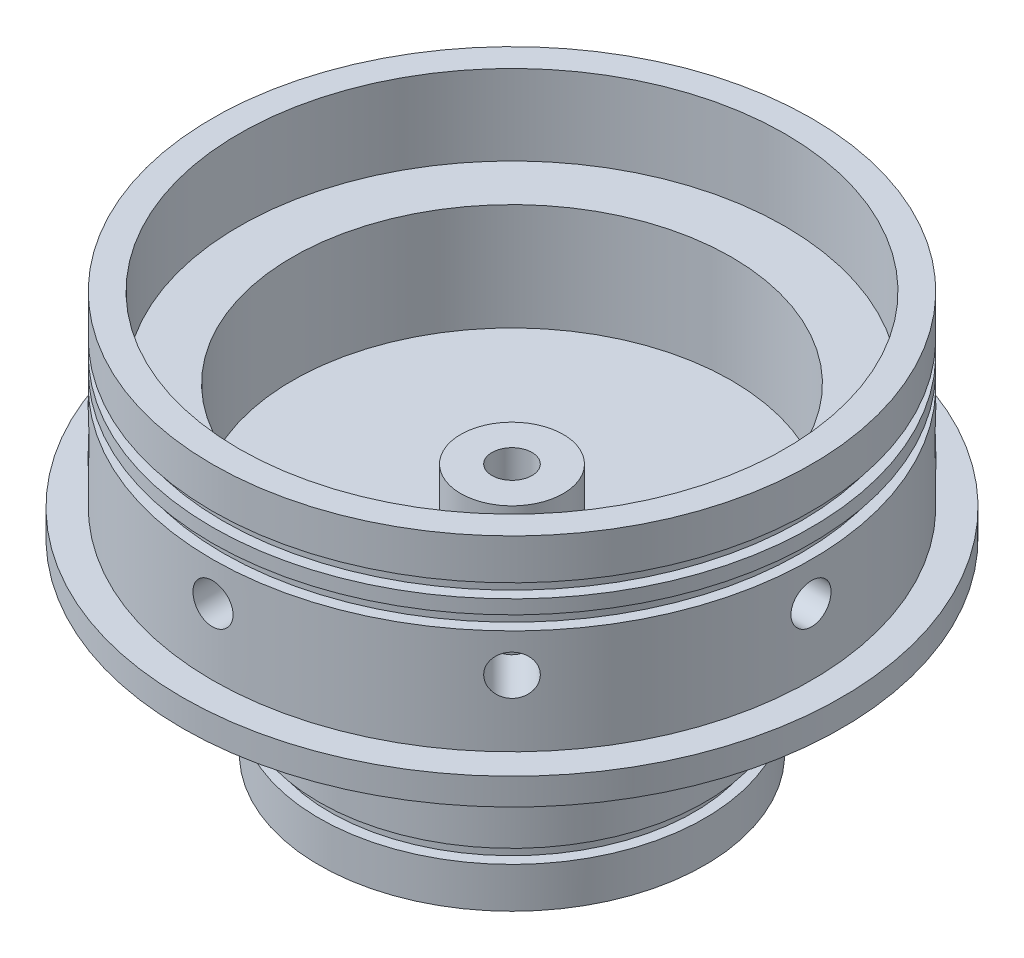
SolidWorks part; units mm, degrees
material "6061-T6 (SS)"
ref_plane "Front Plane" through (0, 0, 0) normal (0, 0, 1) x (1, 0, 0)
ref_plane "Top Plane" through (0, 0, 0) normal (0, 1, 0) x (1, 0, 0)
ref_plane "Right Plane" through (0, 0, 0) normal (1, 0, 0) x (0, 0, -1)
sketch "Sketch1" plane through (0, 0, 0) normal (0, 1, 0) x (1, 0, 0)
  circle A0 centre (0, 0) radius 78.359
extrude "BulkheadPlate" add sketch "Sketch1" along normal blind 6.35 contours A0
sketch "Sketch3" plane through (0, 6.35, 0) normal (0, 1, 0) x (1, 0, 0)
  circle A0 centre (0, 0) radius 71.247
  circle A1 centre (0, 0) radius 52.197
extrude "NosBase" add sketch "Sketch3" along normal blind 25.4
sketch "Sketch4" plane through (0, 31.75, 0) normal (0, 1, 0) x (1, 0, 0)
  circle A0 centre (0, 0) radius 64.897
  circle A1 centre (0, 0) radius 71.247
extrude "NosORings" add sketch "Sketch4" along normal blind 19.05
sketch "Sketch5" plane through (0, 0, 0) normal (0, -1, 0) x (1, 0, 0)
  circle A0 centre (0, 0) radius 45.847
  circle A1 centre (0, 0) radius 26.797
extrude "EngineBase" add sketch "Sketch5" along normal blind 25.4
sketch "Sketch6" plane through (0, -25.4, 0) normal (0, -1, 0) x (-1, 0, 0)
  circle A0 centre (0, 0) radius 39.497
  circle A1 centre (0, 0) radius 45.847
extrude "EngineORings" add sketch "Sketch6" along normal blind 19.05
sketch3d "3DSketch2" plane through (0, 0, 0) normal (0, 0, 1) x (1, 0, 0)
sketch "Sketch7" plane through (0, 0, 71.247) normal (0, 0, 1) x (1, 0, 0)
  line L0 (0, 6.2398) -> (0, 22.1148)
  circle A0 centre (0, 22.1148) radius 4.7625
extrude "NosBoltHole" cut sketch "Sketch7" against normal blind 12.7 contours A0 region at (3.2723, 18.8425, 71.247)
sketch "Sketch9" plane through (0, 0, 0) normal (0, 0, 1) x (1, 0, 0)
  line L0 (0, 0) -> (0, 72.7405)
pattern_circular "NosBoltHoles" count 8 over 360 about axis through (0, 0, 0) along (0, 1, 0) of "NosBoltHole" reverse direction yes
sketch "Sketch13" plane through (0, 0, 0) normal (0, 0, 1) x (1, 0, 0)
  line L0 (0, 0) -> (0, 50.8)
  line L1 (0, 50.8) -> (-71.247, 50.8)
  line L2 (-71.247, 50.8) -> (-71.247, 6.35)
  line L3 (-71.247, 50.8) -> (-71.247, 41.148)
  line L4 (-71.247, 41.148) -> (-68.707, 41.148)
  line L5 (-68.707, 41.148) -> (-68.707, 37.846)
  line L6 (-68.707, 37.846) -> (-71.247, 37.846)
  line L7 (-71.247, 37.846) -> (-71.247, 34.544)
  line L8 (-71.247, 34.544) -> (-68.707, 34.544)
  line L9 (-68.707, 34.544) -> (-68.707, 31.242)
  line L10 (-68.707, 31.242) -> (-71.247, 31.242)
revolve "NosORingChannel" cut sketch "Sketch13" angle 360 about L0 region at (-69.977, 39.497, 0) region at (-69.977, 32.893, 0)
sketch3d "3DSketch3" plane through (0, 0, 0) normal (0, 0, 1) x (1, 0, 0)
sketch "Sketch11" plane through (0, 0, 45.847) normal (0, 0, 1) x (1, 0, 0)
  circle A0 centre (0, -15.875) radius 4.7625
extrude "EngineBoltHole" cut sketch "Sketch11" against normal blind 12.7
pattern_circular "EngineBoltHoles" count 8 over 360 about axis through (0, 0, 0) along (0, 1, 0) of "EngineBoltHole"
sketch "Sketch12" plane through (0, 0, 0) normal (0, 0, 1) x (1, 0, 0)
  line L0 (0, 0) -> (0, -44.45)
  line L1 (0, -44.45) -> (-45.847, -44.45)
  line L2 (-45.847, 0) -> (-45.847, -44.45)
  line L3 (-45.847, -20.6375) -> (-45.847, -44.45) construction
  line L4 (-45.847, -34.798) -> (-43.307, -34.798)
  line L5 (-43.307, -34.798) -> (-43.307, -31.496)
  line L6 (-43.307, -31.496) -> (-45.847, -31.496)
  line L8 (-45.847, -34.798) -> (-45.847, -31.496)
revolve "EngineORingChannel" cut sketch "Sketch12" angle 360 about L0 region at (-44.577, -33.147, 0)
sketch "Sketch14" plane through (0, 6.35, 0) normal (0, 1, 0) x (1, 0, 0)
  circle A0 centre (0, 0) radius 12.192
extrude "InjectorPort" add sketch "Sketch14" along normal blind 8.89
sketch "Sketch10" plane through (0, 6.35, 0) normal (0, 1, 0) x (1, 0, 0)
  circle A0 centre (0, 0) radius 4.7625
extrude "InjectorTap" cut sketch "Sketch10" against normal through all both and the other way through all
